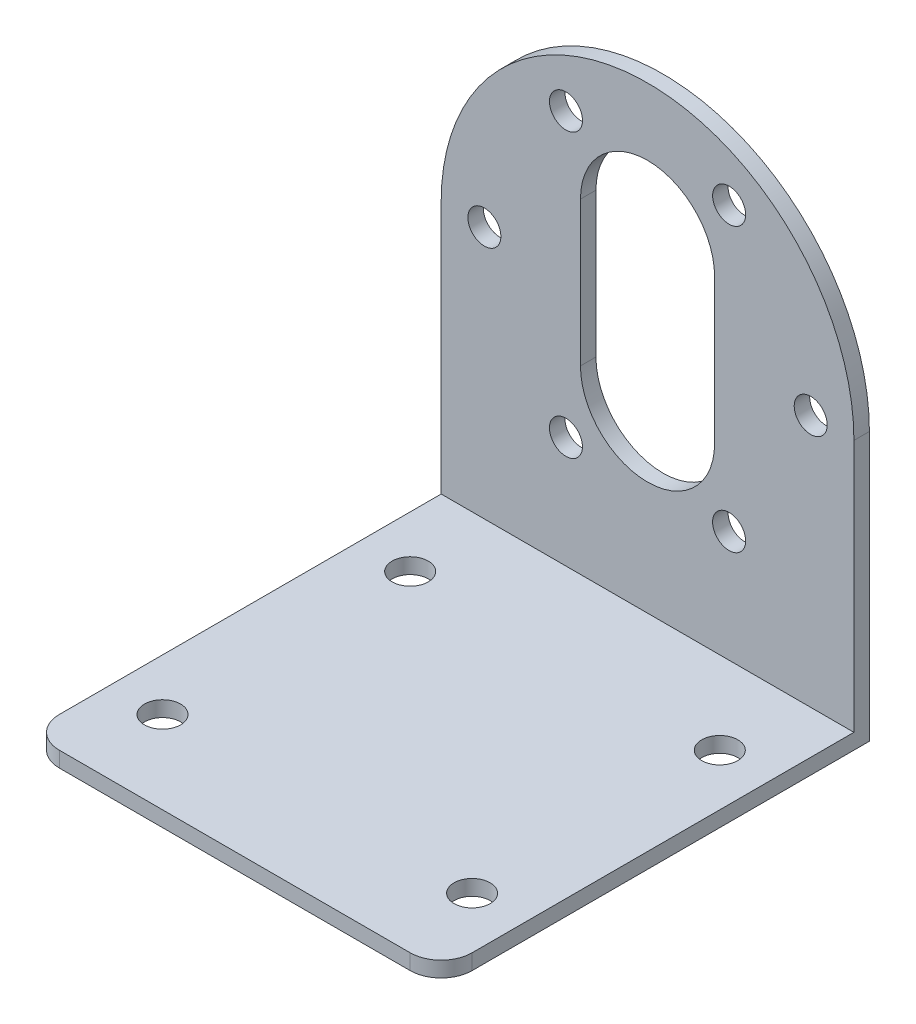
SolidWorks part; units mm, degrees
ref_plane "Front Plane" through (0, 0, 0) normal (0, 0, 1) x (1, 0, 0)
ref_plane "Top Plane" through (0, 0, 0) normal (0, 1, 0) x (1, 0, 0)
ref_plane "Right Plane" through (0, 0, 0) normal (1, 0, 0) x (0, 0, -1)
sketch "Sketch1" plane through (0, 0, 0) normal (0, 1, 0) x (1, 0, 0)
  line L1 (-20, 20) -> (20, 20)
  line L2 (-20, 20) -> (-20, -20)
  line L3 (-20, -20) -> (20, -20)
  line L4 (20, 20) -> (20, -20)
  circle A0 centre (-15, -12) radius 1.75
  circle A1 centre (15, -12) radius 1.75
  circle A2 centre (15, 12) radius 1.75
  circle A3 centre (-15, 12) radius 1.75
  point P4 (-20, -12)
  dimension "D1" = 2
  dimension "D2" = 2
extrude "Boss-Extrude1" add sketch "Sketch1" along normal blind 1.5
fillet "Fillet1" radius 3 2 edges at (20, 0.75, 20) (-20, 0.75, 20)
sketch "Sketch2" plane through (0, 0, -20) normal (0, 0, -1) x (-1, 0, 0)
  line L1 (-20, 0) -> (20, 0)
  line L2 (-20, 0) -> (-20, 26)
  line L4 (20, 0) -> (20, 26)
  line L6 (-6.5, 33) -> (-6.5, 19)
  line L8 (6.5, 33) -> (6.5, 19)
  arc A0 (20, 26) -> (-20, 26) centre (0, 26) ccw
  arc A1 (6.5, 33) -> (-6.5, 33) centre (0, 33) ccw
  arc A2 (-6.5, 19) -> (6.5, 19) centre (0, 19) ccw
  circle A4 centre (15.8117, 26) radius 1.6
  circle A5 centre (7.9059, 12.3067) radius 1.6
  circle A6 centre (-7.9059, 12.3067) radius 1.6
  circle A7 centre (-15.8117, 26) radius 1.6
  circle A8 centre (-7.9059, 39.6933) radius 1.6
  circle A9 centre (7.9059, 39.6933) radius 1.6
  point P30 (0, 26)
  dimension "D1" = 6
extrude "Boss-Extrude2" add sketch "Sketch2" along normal blind 1.5
ref_axis "Wheel axis" through (0, 33, -21.5) along (0, 0, 1)
